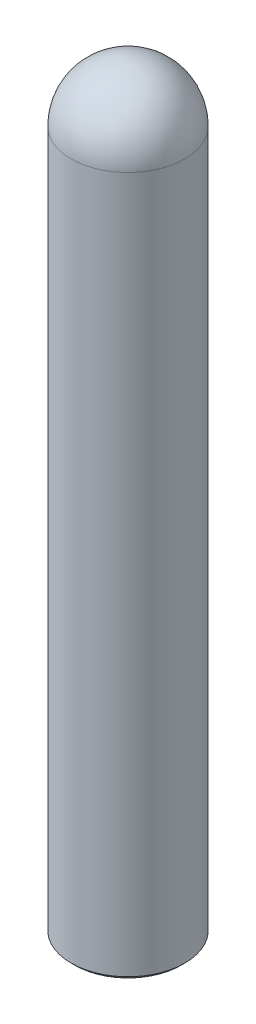
SolidWorks part; units mm, degrees
material "Custom Plastic"
ref_plane "Front Plane" through (0, 0, 0) normal (0, 0, 1) x (1, 0, 0)
ref_plane "Top Plane" through (0, 0, 0) normal (0, 1, 0) x (1, 0, 0)
ref_plane "Right Plane" through (0, 0, 0) normal (1, 0, 0) x (0, 0, -1)
sketch "Sketch1" plane through (0, 0, 0) normal (0, 1, 0) x (1, 0, 0)
  circle A0 centre (0, 0) radius 15
  dimension "D1" = 30
extrude "Boss-Extrude1" add sketch "Sketch1" along normal blind 200
fillet "Fillet1" radius 15 1 edges at (0, 200, 15)
sketch "Sketch2" plane through (0, 0, 0) normal (0, -1, 0) x (1, 0, 0)
  circle A0 centre (0, 0) radius 3.175
  dimension "D1" = 6.35
extrude "Cut-Extrude1" cut sketch "Sketch2" against normal blind 12
chamfer "Chamfer1" distance 0.4 angle 45 1 edges at (0, 0, -3.175)
chamfer "Chamfer2" distance 1 angle 45 1 edges at (0, 0, 15)
